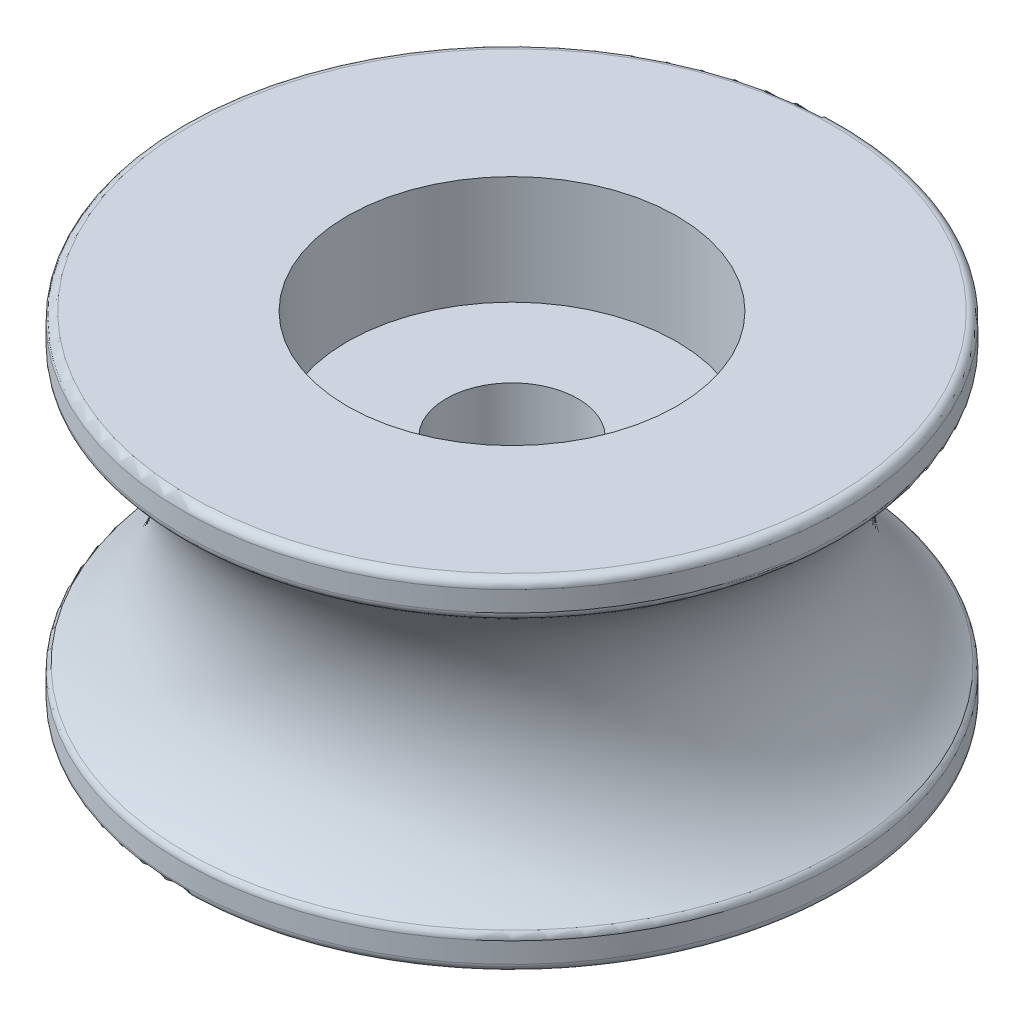
SolidWorks part; units mm, degrees
ref_plane "Piano frontale" through (0, 0, 0) normal (0, 0, 1) x (1, 0, 0)
ref_plane "Piano superiore" through (0, 0, 0) normal (0, 1, 0) x (1, 0, 0)
ref_plane "Piano destro" through (0, 0, 0) normal (1, 0, 0) x (0, 0, -1)
sketch "Schizzo5" plane through (0, 0, 0) normal (0, 0, 1) x (1, 0, 0)
  line L1 (4, 10.35) -> (20, 10.35) construction
  line L2 (4, 10.35) -> (4, -10.35) construction
  line L3 (4, -10.35) -> (20, -10.35) construction
  line L4 (20, 10.35) -> (20, -10.35) construction
  line L5 (20, 10.35) -> (20, 8.35)
  line L6 (20, -10.35) -> (20, -8.35)
  line L7 (4, 10.35) -> (0, 10.35) construction
  line L8 (0, 10.35) -> (0, -10.35) construction
  line L9 (0, -10.35) -> (4, -10.35) construction
  line L10 (4, 3.75) -> (4, -3.75)
  line L11 (10, 10.35) -> (10, 3.75)
  line L12 (10, 3.75) -> (4, 3.75)
  line L13 (10, 10.35) -> (20, 10.35)
  line L14 (10, -10.35) -> (10, -3.75)
  line L15 (10, -3.75) -> (4, -3.75)
  line L16 (10, -10.35) -> (20, -10.35)
  arc A0 (20, 8.35) -> (20, -8.35) centre (25.5025, 0) ccw
  dimension "D3" = 10
  dimension "D1" = 20.7
  dimension "D2" = 16
  dimension "D4" = 2
  dimension "D5" = 2
  dimension "D6" = 4
  dimension "D8" = 6.6
  dimension "D9" = 6
  dimension "D10" = 6.6
  dimension "D11" = 6
revolve "Rivoluzione12" add sketch "Schizzo5" angle 360 about L8
fillet "Raccordo1" radius 0.5 4 edges at (-20, -10.35, 0) (-20, -8.35, 0) (-20, 10.35, 0) (-20, 8.35, 0)
